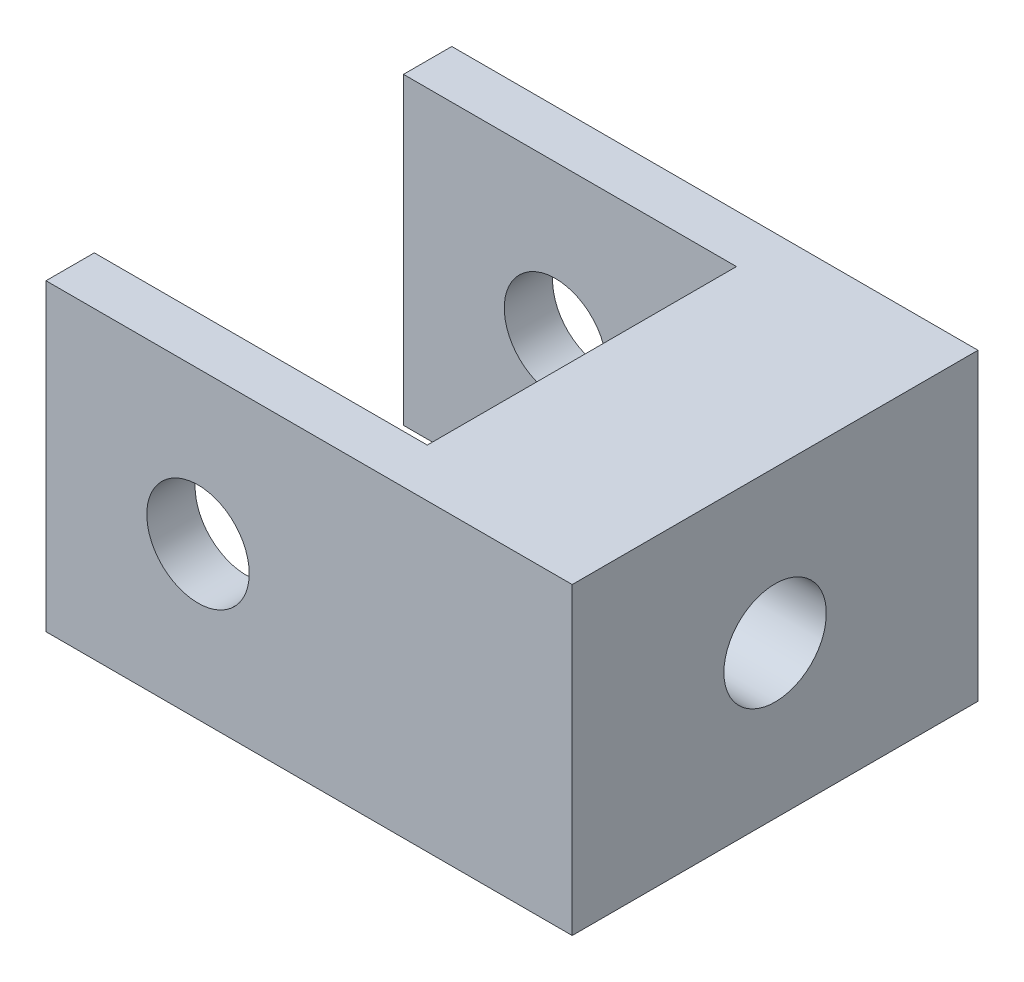
SolidWorks part; units mm, degrees
material "ABS"
ref_plane "Front Plane" through (0, 0, 0) normal (0, 0, 1) x (1, 0, 0)
ref_plane "Top Plane" through (0, 0, 0) normal (0, 1, 0) x (1, 0, 0)
ref_plane "Right Plane" through (0, 0, 0) normal (1, 0, 0) x (0, 0, -1)
sketch "Belt Tensioner Sketch" plane through (0, 0, 0) normal (0, 0, 1) x (1, 0, 0)
  line L0 (-5.8426, -30.4475) -> (-5.8426, 24.5525) construction
  line L1 (0.3507, 26.0262) -> (12.7372, -26.0262) construction
  line L2 (-24.4223, -26.0262) -> (-12.0358, 26.0262) construction
  line L3 (6.544, 0) -> (19.3662, 0) construction
  line L4 (6.544, 0) -> (0, 0) construction
  line L5 (0, -7.8662) -> (9.3662, -7.8662)
  line L6 (9.3662, -7.8662) -> (9.3662, 7.8662)
  line L7 (9.3662, 7.8662) -> (0, 7.8662)
  line L8 (9.3662, 7.8662) -> (19.3662, 7.8662)
  line L9 (19.3662, 7.8662) -> (19.3662, -7.8662)
  line L10 (19.3662, -7.8662) -> (9.3662, -7.8662)
  line L11 (9.3662, 5) -> (14.3662, 5) construction
  line L12 (14.3662, 5) -> (14.3662, -5) construction
  line L13 (14.3662, -5) -> (9.3662, -5) construction
  line L14 (14.3662, -2.5) -> (19.3662, -2.5) construction
  line L15 (19.3662, 2.5) -> (14.3662, 2.5) construction
  line L16 (6.544, 7.8662) -> (6.544, -7.8662) construction
  line L17 (14.3662, -2.5) -> (19.3662, 2.5) construction
  line L18 (0, 7.8662) -> (-7.8662, 7.8662)
  line L19 (-7.8662, 7.8662) -> (-7.8662, -7.8662)
  line L20 (-7.8662, -7.8662) -> (0, -7.8662)
  circle A0 centre (-5.8426, 24.5525) radius 6.3662 construction
  circle A1 centre (-5.8426, -30.4475) radius 19.0986 construction
  circle A2 centre (0, 0) radius 6.3662 construction
  arc A3 (0, 7.8662) -> (0, -7.8662) centre (0, 0) ccw construction
  point P28 (16.8662, 0)
  point P31 (14.3662, 0)
  dimension "DrivePitchDiameter" = 12.7324
  dimension "OutputPD" = 38.1972
  dimension "CenterDistance" = 55
  dimension "D1" = 9.3662
  dimension "D2" = 10
  dimension "D3" = 5
  dimension "D4" = 1.5
  dimension "D5" = 5
  dimension "D6" = 10
extrude "Body Extrude" add sketch "Belt Tensioner Sketch" along normal mid plane 21 contours L7 A3 L5 L6 | L10 L9 L8 L6 region at (0.75, 0, 0) region at (14.3662, 0, 0)
extrude "Cut-Extrude1" cut sketch "Belt Tensioner Sketch<3>" against normal mid plane 16 contours L7 A3 L5 L6 region at (0.75, 0, 0)
sketch "Belt Tensioner Sketch<3>" plane through (0, 0, 0) normal (0, 0, 1) x (1, 0, 0) same geometry as "Belt Tensioner Sketch"
hole_wizard "CBORE for M5 SHCS1" positions "Sketch3" profile "Sketch4" counterbore size "M5" standard "ANSI Metric" end condition through all
sketch "Sketch3" plane through (9.3662, 0, 0) normal (-1, 0, 0) x (0, 0, 1)
  point P0 (0, 0)
sketch "Sketch4" plane through (9.3662, 0, 0) normal (0, 1, 0) x (0, 0, 1)
  line L0 (0, 0) -> (0, 10)
  line L1 (0, 10) -> (2.65, 10)
  line L3 (2.65, 10) -> (2.65, 5)
  line L4 (2.65, 5) -> (5, 5)
  line L5 (5, 5) -> (5, 0)
  line L7 (5, 0) -> (0, 0)
  line L11 (0, -6.35) -> (0, 107.95) construction
  dimension "Thru Hole Dia." = 5.3
  dimension "Thru Hole Depth" = 10
  dimension "C'Bore Dia." = 10
  dimension "C'Bore Depth" = 5
hole_wizard "M5 Clearance Hole1" positions "Sketch7" profile "Sketch8" hole size "M5" standard "ANSI Metric" end condition through all
sketch "Sketch7" plane through (0, 0, 10.5) normal (0, 0, 1) x (1, 0, 0)
  point P0 (0, 0)
sketch "Sketch8" plane through (0, 0, 10.5) normal (1, 0, 0) x (0, -1, 0)
  line L0 (0, 0) -> (0, 21)
  line L1 (0, 21) -> (2.65, 21)
  line L2 (2.65, 21) -> (2.65, 0)
  line L5 (2.65, 0) -> (0, 0)
  line L11 (0, -6.35) -> (0, 107.95) construction
  dimension "Thru Hole Dia." = 5.3
  dimension "Thru Hole Depth" = 21
equation "\"ExtrusionStandard\"= 20mm'Size of extrusion used for framing"
equation "\"BaseExtrusionFrameWidth\"= 60mm'Width of the central aluminum extrusion"
equation "\"BaseExtrusionFrameHeight\"= 20mm'Height of the central aluminum extrusion"
equation "\"PlateThickness\"= 15mm'Thickness of the the front and back framing plates"
equation "\"RailHeight\"= 13mm'Total height of the carriage and rail component"
equation "\"WallThickness\"= 3mm'Standard wall thickness"
equation "\"ShaftDiameter\"= 20mm'Outside Diameter of the main yoke shaft"
equation "\"ShaftClearance\"= 1mm'Clearance/gap between the main yoke and non-bearing elements"
equation "\"PlainBearingBoltCircleDiameter\"= ( \"WallThickness\" + \"M3_ClearanceDiameter\" / 2 ) * 2 + \"PlainBearingOD\"'Bolt circle diameter for the plain bearing retainer/mount"
equation "\"PlainBearingBoltcount\"= 5'Number of bolts used in the plain bearing/mount"
equation "\"X_ThrustBearingOD\"= 35mm'OD of the thrust bearing used on the main shaft"
equation "\"X_ThrustBearingID\"= 20mm'ID of the thrust bearing used on the main shaft"
equation "\"X_ThrustBearingThickness\"= 10mm'Thickness of the thrust bearing used on the main shaft"
equation "\"X_RearCollarOD\"= 32mm'OD of the shaft collar of the main shaft"
equation "\"X_RearCollarID\"= 20mm'ID of the shaft collar of the main shaft"
equation "\"X_RearCollarThickness\"= 8mm'Thickness of the collar along the main shaft"
equation "\"LeadScrewDiameter\"= 6.35mm'OD of the leadsrew used on the Y axis"
equation "\"LeadScrewHeight\"= 10mm'Height of the center of the Lead screw from bottom of gantry extrusion"
equation "\"LeadScrewNut_FlangeOD\"= 25mm'OD of the lead screw nut flange"
equation "\"LeadScrewNut_BoltCircleDiameter\"= 19mm'Bolt circle diameter needed to mount the leadscrew nut"
equation "\"LeadScrewNut_BoltCount\"= 6'Number of bolts required to mount the leadscrew nut to gantry."
equation "\"Pillow_BaseClearance\"= 6mm + \"WallThickness\"'Pillow block base needed to internally mount screws"
equation "\"X_PillowHeight\"= \"Pillow_BaseClearance\" + \"calc_X_PillowRadius\"'Height of the main shaft pillow block base, as measured from the top of the gantry surface"
equation "\"X_BeltPitch\"= 2mm'Pitch of the timing belt used on the X axis/main shaft."
equation "\"X_Drive_Teeth\"= 20'Number of teeth used on the X/Main stepper motor pulley"
equation "\"X_Shaft_Teeth\"= 60'Number of teeth on the X/Main shaft pulley"
equation "\"X_Drive_PD\"= ( \"X_Drive_Teeth\" * \"X_BeltPitch\" ) / PI'Pitch Diameter of the X/main motor pulley"
equation "\"X_Shaft_PD\"= ( \"X_Shaft_Teeth\" * \"X_BeltPitch\" ) / PI'Pitch Diameter of the X/main shaft pulley"
equation "\"X_CenterDistance\"= 55mm'Distance between the main shaft and motor pulley centers"
equation "\"GantryLength\"= 150mm'Length of the gantry extrusion/plate"
equation "\"X_MotorPlateThickness\"= 15mm'Thickness of the plate used to hold the X/main motor"
equation "\"X_MotorPlateLength\"= \"X_MotorPlateThickness\" + \"ExtrusionStandard\" * 2'FIXME"
equation "\"X_BeltWidth\" = 9mm'Width of the timing belt used on the X/Main shaft rotary drive"
equation "\"X_PillowLength\"= ( \"WallThickness\" * 4 ) + \"X_RearCollarThickness\" + ( \"X_ThrustBearingThickness\" * 2 ) + \"X_ShaftRotaryBearingThickness\"'Total length of the pillow block used to hold the main shaft"
equation "\"X_ShaftRotaryBearingThickness\"= 9mm'Thickness of the radial bearing used on the main shaft"
equation "\"X_ShaftRotaryBearingOD\"= 37mm'OD of the radial bearing used on the main shaft"
equation "\"ShaftLength\"= 400mm'Length of the main shaft."
equation "\"PlainBearingOD\"= 31.8mm'OD of the Plain Bearing housing"
equation "\"Y_Drive_Length\"= \"ShaftLength\"'duplicate"
equation "\"Y_Drive_Diameter\"= \"LeadScrewDiameter\"'duplicate"
equation "\"Y_Drive_ThrustBearingOD\"= .5625in'OD of the thrust bearings used to support the leadscrew/Y drive"
equation "\"Y_Drive_ThrustBearingThickness\"= .193in'Thickness of the thrust bearings used to support the leadscrew/Y drive"
equation "\"Y_Drive_ShaftCollarOD\"= .6875in'OD of the collar used to constrain the leadscrew/Y drive"
equation "\"Y_Drive_ShaftCollarThickness\"= .3125in'Thickness of the collar used to constrain the leadscrew/Y drive"
equation "\"Y_Drive_ShaftCollarClearance\"= .375in / 2'Amount of radial clearance needed around the leadscrew/Y shaft collar"
equation "\"calc_Y_Drive_BearingLargestDiameter\"= IIF ( \"Y_Drive_ThrustBearingOD\" > \"Y_Drive_ShaftCollarOD\" , \"Y_Drive_ThrustBearingOD\" , \"Y_Drive_ShaftCollarOD\" )'FIXME - calculated diameter needed for Y drive pillow - needs to account for collar clearance."
equation "\"Y_Drive_BearingBoltCircleDiameter\"= \"calc_Y_Drive_BearingLargestDiameter\" + ( \"Y_Drive_ShaftCollarClearance\" * 2 ) + ( \"WallThickness\" * 2 ) + 2 * 10mm'FIXME - unused?"
equation "\"M3_ClearanceDiameter\"= 8mm'Keepout diameter for M3 holes"
equation "\"M5_ClearanceDiameter\"= 10mm'Keepout Diameter for M5 holes"
equation "\"Y_Drive_CenterDistance\"= 65mm'Center Distance between Y motor drive and leadscrew pulley"
equation "\"Y_Drive_Teeth\"= 20'Number of teeth on the Y/linear stepper pulley"
equation "\"Y_Drive_ShaftTeeth\"= 60'Number of teeth on the Y/linear leadscrew pulley"
equation "\"Y_Drive_BeltWidth\"= 9mm'Width of the belt used on the Y/linear drive"
equation "\"Y_Drive_BeltPitch\"= 2mm'Pitch of the timing belt used on the Y/linear drive"
equation "\"Y_Drive_PD\"= ( \"Y_Drive_Teeth\" * \"Y_Drive_BeltPitch\" ) / PI'Pitch Diameter of the stepper pulley for the Y/linear drive"
equation "\"Y_Drive_ShaftPD\"= ( \"Y_Drive_ShaftTeeth\" * \"Y_Drive_BeltPitch\" ) / PI'Pitch diameter of the pulley on the Y/linear leadscrew"
equation "\"PlainBearingLength\"= 44.8mm'Length of the plain bearing housing"
equation "\"Y_Drive_ShaftBearingThickness\"= .196in'Thickness of the radial bearing used to support the Y leadscrew"
equation "\"Y_Drive_ShaftBearingOD\"= .625in'OD of the radial bearing used to support the Y leadscrew"
equation "\"EncoderMount_BoltWidth\"= 80mm"
equation "\"EncoderMount_BoltRowCount\" = 1"
equation "\"EncoderMount_BoltRowDistance\"= 20mm"
equation "\"EncoderMount_Offset\"= 10mm"
equation "\"Y_Drive_StepperShaftLength\"= 21mm"
equation "\"X_StepperShaftLength\" = 21mm"
equation "\"Y_DriveStepperShaftDiameter\"= 6.35mm"
equation "\"X_StepperShaftDiameter\"= 6.35mm"
equation "\"calc_X_PillowRadius\"= IIF ( ( \"X_ThrustBearingOD\" / 2 ) > ( \"X_RearCollarOD\" / 2 * 1.5 ) , \"X_ThrustBearingOD\" / 2 , ( \"X_RearCollarOD\" / 2 ) * 1.5 ) + ( \"WallThickness\" )'Minimum Radius needed for X/main shaft pillow block elements."
equation "\"calc_Y_PillowRadius\"= IIF ( \"Y_Drive_ThrustBearingOD\" / 2 > ( \"Y_Drive_ShaftCollarOD\" / 2 * 1.5 ) , \"Y_Drive_ThrustBearingOD\" / 2 , ( \"Y_Drive_ShaftCollarOD\" / 2 ) * 1.5 )'Minimum radius needed for the Y/linear shaft pillow block elements"
equation "\"Y_PillowHeight\"= \"Pillow_BaseClearance\" + \"calc_Y_PillowRadius\"'Height of the Y/linear pillow block base"
equation "\"Assembly_MainShaftStickout\"= 50mm'Amount of stickout at maximum pitch down (yoke forward)"
equation "\"GantryHeight\"= \"ExtrusionStandard\"'Height of the Gantry, including carriage mounting brackets"
equation "\"Y_StepperFrameSize\"= 57mm"
equation "\"Y_StepperHoleMountingDistance\"= 47mm"
equation "\"SidePanelHeight\" = \"Y_StepperFrameSize\" / 2 + \"X_CenterDistance\" + \"X_PillowHeight\" + \"GantryHeight\" + \"RailHeight\" + \"ExtrusionStandard\" - ( \"ExtrusionStandard\" * 3 ) + \"TopClearance\""
equation "\"TopClearance\"= 5mm"
equation "\"ExtrusionLength\"= 400mm"
equation "\"TopPanelWidth\" = 150mm"
equation "\"BodyPanelThickness\"= .25in'Thickness of side and top body panels."
equation "\"DrivePitchDiameter@Belt Tensioner Sketch\" = \"X_Drive_PD\""
equation "\"OutputPD@Belt Tensioner Sketch\" = \"X_Shaft_PD\""
equation "\"CenterDistance@Belt Tensioner Sketch\" = \"X_CenterDistance\""
equation "\"D6@Belt Tensioner Sketch\"=\"M5_ClearanceDiameter\""
equation "\"D1@Body Extrude\" = \"X_BeltWidth\" + \"WallThickness\" * 4"
equation "\"D1@Cut-Extrude1\"= \"X_BeltWidth\" + \"WallThickness\" * 2 + 1mm"
equation "\"D1@Belt Tensioner Sketch\"=\"X_Drive_PD\"/2+\"WallThickness\""
